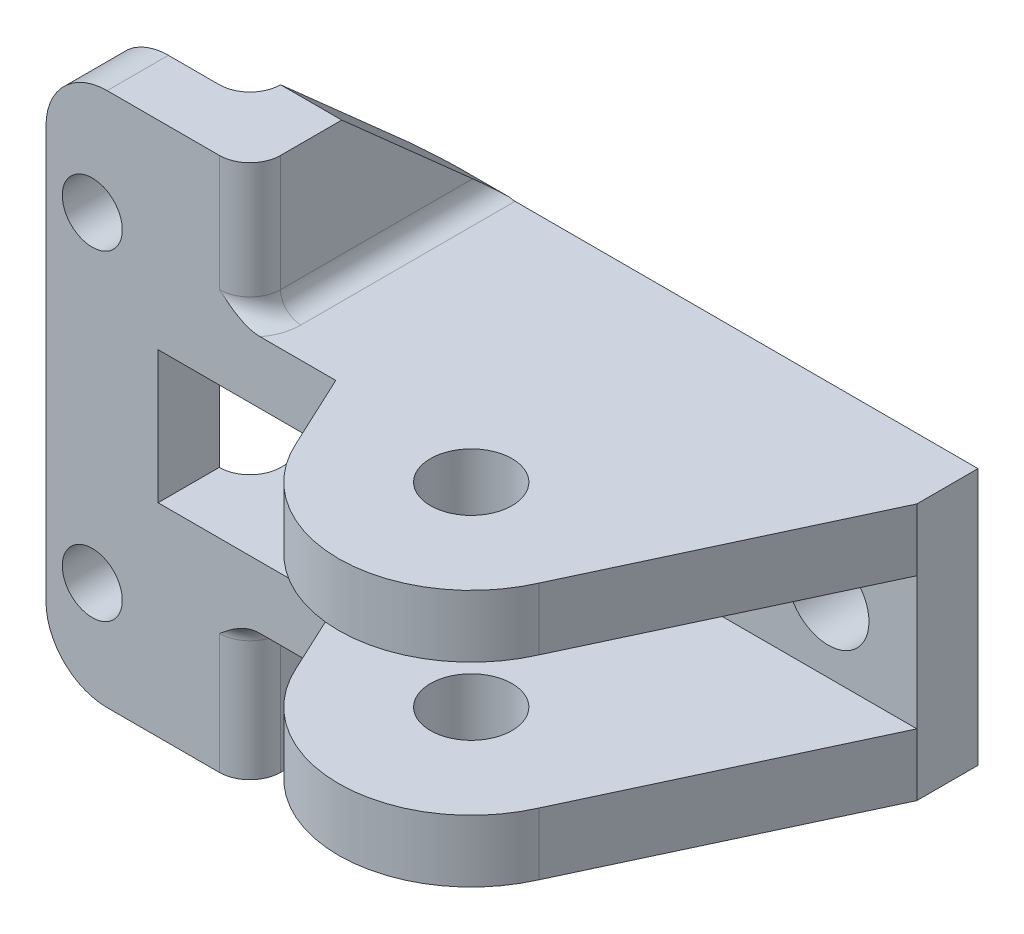
SolidWorks part; units mm, degrees
ref_plane "Plan de face" through (0, 0, 0) normal (0, 0, 1) x (1, 0, 0)
ref_plane "Plan de dessus" through (0, 0, 0) normal (0, 1, 0) x (1, 0, 0)
ref_plane "Plan de droite" through (0, 0, 0) normal (1, 0, 0) x (0, 0, -1)
sketch "Esquisse1" plane through (0, 0, 0) normal (0, 0, 1) x (1, 0, 0)
  line L0 (5.8555, 18.596) -> (5.8555, 5.996)
  line L1 (-17.8397, 18.596) -> (5.8555, 18.596)
  line L2 (-17.8397, 5.996) -> (5.8555, 5.996)
  line L3 (-17.8397, 18.596) -> (-17.8397, 5.996)
  circle A0 centre (-13.4897, 12.426) radius 2
  circle A1 centre (1.5103, 12.426) radius 2
  point P8 (0, 0)
  dimension "D1" = 4
  dimension "D2" = 4.35
extrude "Boss.-Extru.1" add sketch "Esquisse1" along normal blind 3
sketch "Esquisse3" plane through (0, 5.996, 0) normal (0, -1, 0) x (1, 0, 0)
  line L1 (-17.8397, 3) -> (5.8555, 3)
  line L3 (-17.8397, 3) -> (5.8555, 3) construction
  line L4 (-17.8397, 3) -> (-11.9427, 15.6155)
  line L5 (5.8555, 3) -> (-0.0415, 15.6155)
  line L6 (-5.9921, 11) -> (-5.9921, 30.38) construction
  circle A0 centre (-5.9921, 13) radius 2
  arc A1 (-0.0415, 15.6155) -> (-11.9427, 15.6155) centre (-5.9921, 13) ccw
  dimension "D2" = 10
extrude "Boss.-Extru.2" add sketch "Esquisse3" against normal blind 12.6
sketch "Esquisse6" plane through (0, 18.596, 0) normal (0, 1, 0) x (1, 0, 0)
  line L1 (-17.8397, 0) -> (-19.3397, 0)
  line L2 (-17.8397, 0) -> (-17.8397, -3)
  line L13 (-17.8397, 0) -> (-19.3397, 0)
  line L14 (-17.8397, 0) -> (-17.8397, -10.5)
  line L15 (-19.3397, -12) -> (-19.9448, -12)
  line L16 (-20.8397, -1.5) -> (-20.8397, -7.5)
  line L17 (-19.3397, -12) -> (-27.8397, -12)
  line L18 (-17.8397, -10.5) -> (-17.8397, -8.3919)
  line L19 (-22.3397, -9) -> (-27.8397, -9)
  line L20 (-27.8397, -12) -> (-27.8397, -9)
  arc A0 (-19.3397, -12) -> (-17.8397, -10.5) centre (-19.3397, -10.5) ccw
  arc A1 (-19.3397, 0) -> (-20.8397, -1.5) centre (-19.3397, -1.5) ccw
  arc A2 (-20.8397, -7.5) -> (-22.3397, -9) centre (-22.3397, -7.5) cw
  point P18 (-20.8397, -9)
  line M6 (-17.8397, 0) -> (-17.8397, -3)
  dimension "D5" = 1.5
  dimension "D1" = 6
  dimension "D2" = 3
  dimension "D4" = 7
extrude "Boss.-Extru.4" add sketch "Esquisse6" along normal blind 6.7 and the other way blind 19.5 contours L16 A2 L19 L20 L17 L15 A0 L14 L1 A1 M6 region at (-17.9959, 18.596, 1.5)
sketch "Esquisse7" plane through (-20.8397, 0, 0) normal (-1, 0, 0) x (0, 0, 1)
  line L0 (-6.1403, 12.196) -> (-6.427, 7.7538)
  line L2 (7.5, 25.296) -> (-0.0693, 18.5749)
  line L3 (-0.0693, 18.5749) -> (-0.4662, 12.196)
  line L9 (-0.4662, 12.196) -> (-16.8604, 12.196) construction
  line L12 (-6.1403, 12.196) -> (-6.427, 16.6381)
  line L13 (-6.427, 16.6381) -> (-3.7725, 30.9309)
  line L14 (-3.7725, 30.9309) -> (6.0598, 29.411)
  line L15 (6.0598, 29.411) -> (7.5, 25.296)
  line L16 (-0.0693, 5.817) -> (-0.4662, 12.196)
  line L17 (6.0598, -5.019) -> (7.5, -0.904)
  line L18 (7.5, -0.904) -> (-0.0693, 5.817)
  line L19 (-3.7725, -6.539) -> (6.0598, -5.019)
  line L20 (-6.427, 7.7538) -> (-3.7725, -6.539)
extrude "Enlèv. mat.-Extru.2" cut sketch "Esquisse7" against normal blind 3
sketch "Esquisse8" plane through (0, 5.996, 0) normal (0, -1, 0) x (-1, 0, 0)
  line L0 (17.8397, 0) -> (-5.8555, 0) construction
  line L1 (11.3046, 0) -> (19.7422, 0)
  line L2 (11.3046, 0) -> (11.3046, -12)
  line L3 (11.3046, -12) -> (19.7422, -12)
  line L4 (19.7422, 0) -> (19.7422, -12)
  line L5 (19.3397, -12) -> (27.8397, -12) construction
extrude "Boss.-Extru.5" add sketch "Esquisse8" against normal blind 12.6
sketch "Esquisse5" plane through (5.8555, 0, 0) normal (1, 0, 0) x (0, 0, -1)
  line L0 (-3, 5.996) -> (-3, 18.596) construction
  line L1 (-3, 15.546) -> (-23.6338, 15.546)
  line L2 (-3, 15.546) -> (-3, 9.046)
  line L3 (-3, 9.046) -> (-23.6338, 9.046)
  line L4 (-23.6338, 15.546) -> (-23.6338, 9.046)
  line L6 (-3, 18.596) -> (-15.6155, 18.596) construction
  dimension "D1" = 6.5
  dimension "D2" = 3.05
extrude "Enlèv. mat.-Extru.1" cut sketch "Esquisse5" against normal blind 28.2
fillet "Congé3" radius 1 4 edges at (-18.2791, 18.596, 11.5607) (-18.2791, 5.996, 11.5607) (-17.8397, 18.596, 5.25) (-17.8397, 5.996, 5.25)
sketch "Esquisse9" plane through (0, 0, 0) normal (0, 0, -1) x (-1, 0, 0)
  circle A0 centre (13.4897, 12.426) radius 2
extrude "Enlèv. mat.-Extru.3" cut sketch "Esquisse9" against normal blind 3.6
sketch "Esquisse10" plane through (0, 0, 9) normal (0, 0, -1) x (-1, 0, 0)
  line L0 (34.4362, 1.393) -> (36.5216, 1.393)
  line L1 (39.0616, 3.933) -> (39.0616, 19.153)
  line L2 (36.5216, 21.6992) -> (34.4362, 21.6974)
  line L4 (34.4362, 21.6974) -> (34.4362, 1.393)
  arc A0 (36.5216, 1.393) -> (39.0616, 3.933) centre (36.5216, 3.933) ccw
  arc A1 (39.0616, 19.153) -> (36.5216, 21.6992) centre (36.5154, 19.153) ccw
  circle A2 centre (36.7756, 3.679) radius 1.47
  circle A3 centre (36.7756, 19.407) radius 1.47
sketch "Esquisse11" plane through (0, 0, 9) normal (0, 0, -1) x (-1, 0, 0)
  circle A2 centre (25.5702, 4.0244) radius 1.47
  circle A3 centre (25.5702, 19.7524) radius 1.47
extrude "Enlèv. mat.-Extru.4" cut sketch "Esquisse11" against normal blind 3.6
fillet "Congé4" radius 3 2 edges at (-27.8397, 25.296, 10.5) (-27.8397, -0.904, 10.5)
